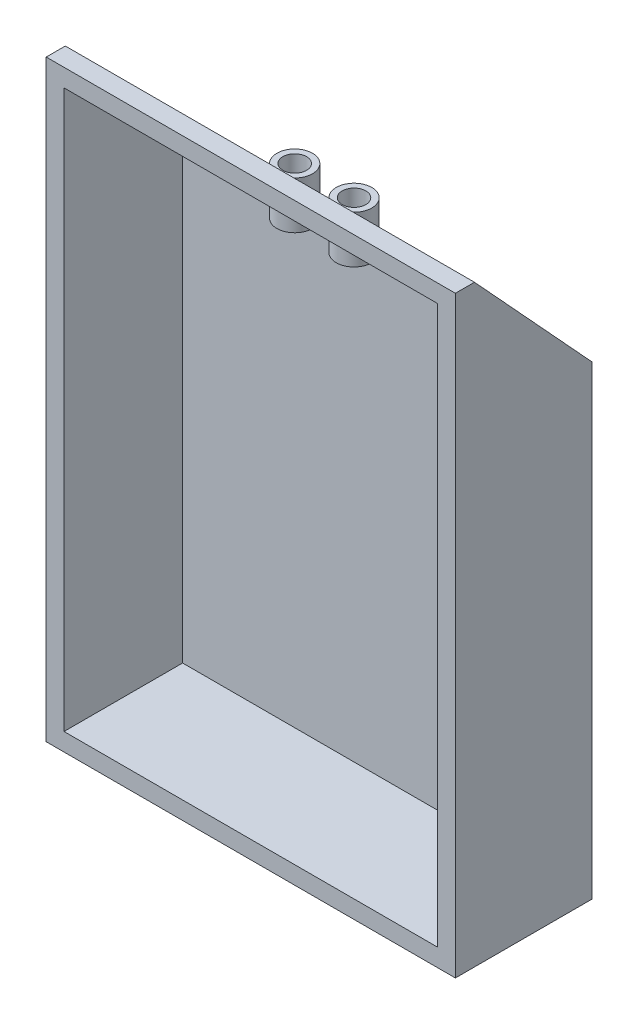
SolidWorks part; units mm, degrees
ref_plane "Ön Düzlem" through (0, 0, 0) normal (0, 0, 1) x (1, 0, 0)
ref_plane "Üst Düzlem" through (0, 0, 0) normal (0, 1, 0) x (1, 0, 0)
ref_plane "Sağ Düzlem" through (0, 0, 0) normal (1, 0, 0) x (0, 0, -1)
sketch "Çizim1" plane through (0, 0, 0) normal (0, 0, 1) x (1, 0, 0)
  line L0 (-34.5, 50) -> (34.5, -50) construction
  line L1 (-34.5, 50) -> (34.5, 50)
  line L2 (-34.5, 50) -> (-34.5, -50)
  line L3 (-34.5, -50) -> (34.5, -50)
  line L4 (34.5, 50) -> (34.5, -50)
  dimension "D1" = 100
  dimension "D2" = 69
extrude "Yükseklik-Ekstrüzyon1" add sketch "Çizim1" along normal blind 3
sketch "Çizim2" plane through (0, 0, 3) normal (0, 0, 1) x (1, 0, 0)
  line L0 (-31.5, 47) -> (-31.5, -47)
  line L1 (-34.5, 50) -> (34.5, 50)
  line L2 (-34.5, 50) -> (-34.5, -50)
  line L3 (-34.5, -50) -> (34.5, -50)
  line L4 (34.5, 50) -> (34.5, -50)
  line L5 (-31.5, -47) -> (31.5, -47)
  line L6 (31.5, 47) -> (31.5, -47)
  line L7 (-31.5, 47) -> (31.5, 47)
  dimension "D1" = 3
extrude "Yükseklik-Ekstrüzyon2" add sketch "Çizim2" along normal blind 20
sketch "Çizim3" plane through (34.5, 0, 0) normal (1, 0, 0) x (0, 0, -1)
  line L0 (-23, 50) -> (0, 25)
  line L1 (0, -50) -> (0, 50) construction
  line L2 (0, 25) -> (0, 50)
  line L3 (0, 50) -> (-23, 50)
extrude "Kes-Ekstrüzyon1" cut sketch "Çizim3" against normal through all
sketch "Çizim4" plane through (34.5, 0, 0) normal (1, 0, 0) x (0, 0, -1)
  line L0 (-23, 50) -> (-19.78, 50)
  line L1 (-19.78, 50) -> (0, 28.5)
  line L2 (0, 28.5) -> (0, 25)
  line L3 (0, 25) -> (-23, 50)
  dimension "D1" = 3.5
extrude "Yükseklik-Ekstrüzyon3" add sketch "Çizim4" against normal through all
sketch "Çizim5" plane through (0, 50, 0) normal (0, 1, 0) x (1, 0, 0)
  line L1 (-34.5, 0) -> (-34.5, -19.78) construction
  circle A0 centre (-5, -10.5942) radius 3
  circle A1 centre (5, -10.5942) radius 3
  dimension "D1" = 10
  dimension "D2" = 29.5
extrude "Kes-Ekstrüzyon2" cut sketch "Çizim5" against normal blind 20
sketch "Çizim6" plane through (0, 50, 0) normal (0, 1, 0) x (1, 0, 0)
  circle A0 centre (-5, -10.5942) radius 3
  circle A1 centre (-5, -10.5942) radius 2
  circle A2 centre (5, -10.5942) radius 3
  circle A3 centre (5, -10.5942) radius 2
extrude "Yükseklik-Ekstrüzyon4" add sketch "Çizim6" along normal blind 8 from offset 15 offset against normal yes
